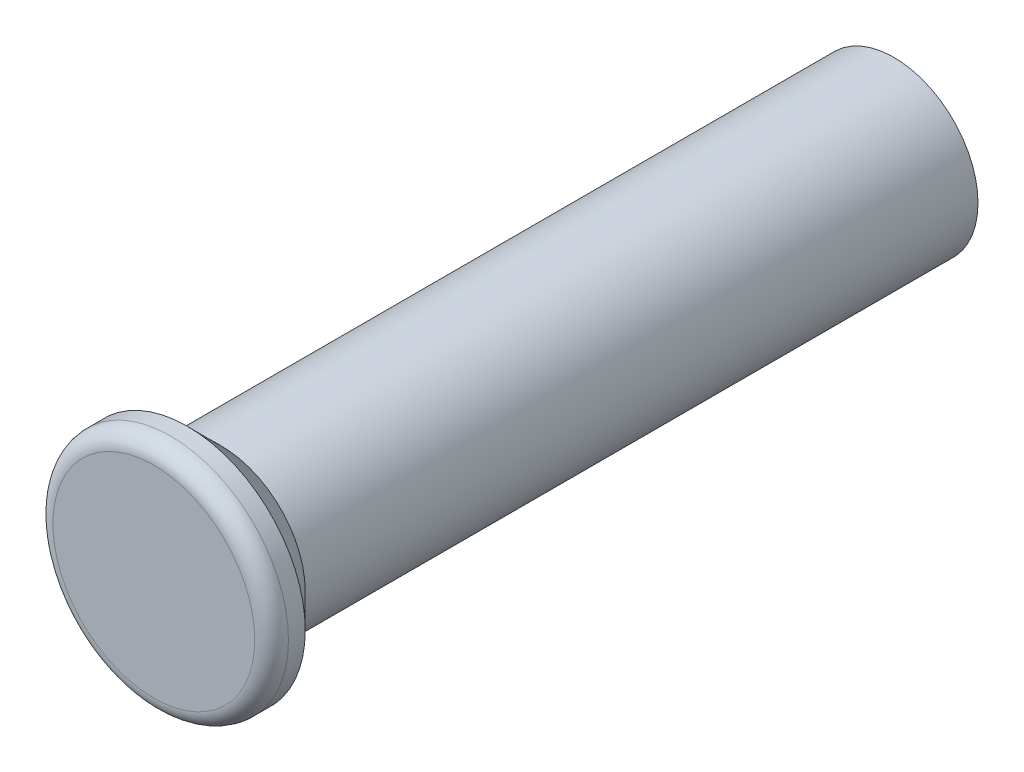
SolidWorks part; units mm, degrees
material "AISI 1045 Steel, cold drawn"
ref_plane "Front Plane" through (0, 0, 0) normal (1, 0, 0) x (0, 1, 0)
ref_plane "Top Plane" through (0, 0, 0) normal (0, 0, 1) x (0, 1, 0)
ref_plane "Right Plane" through (0, 0, 0) normal (0, 1, 0) x (-1, 0, 0)
sketch "Sketch1" plane through (0, 0, 0) normal (0, 0, 1) x (0, 1, 0)
  circle A0 centre (0, 0) radius 2.5
  circle A1 centre (0, 0) radius 3.5
  dimension "D1" = 5
  dimension "D2" = 7
extrude "Boss-Extrude1" add sketch "Sketch1" against normal blind 20 contours A0
extrude "Boss-Extrude2" add sketch "Sketch1<3>" along normal blind 2 contours A1
sketch "Sketch1<3>" plane through (0, 0, 0) normal (0, 0, 1) x (0, 1, 0) same geometry as "Sketch1"
chamfer "Chamfer1" distance 1 angle 45 1 edges at (3.5, 0, 0)
fillet "Fillet1" radius 0.5 1 edges at (3.5, 0, 2)
